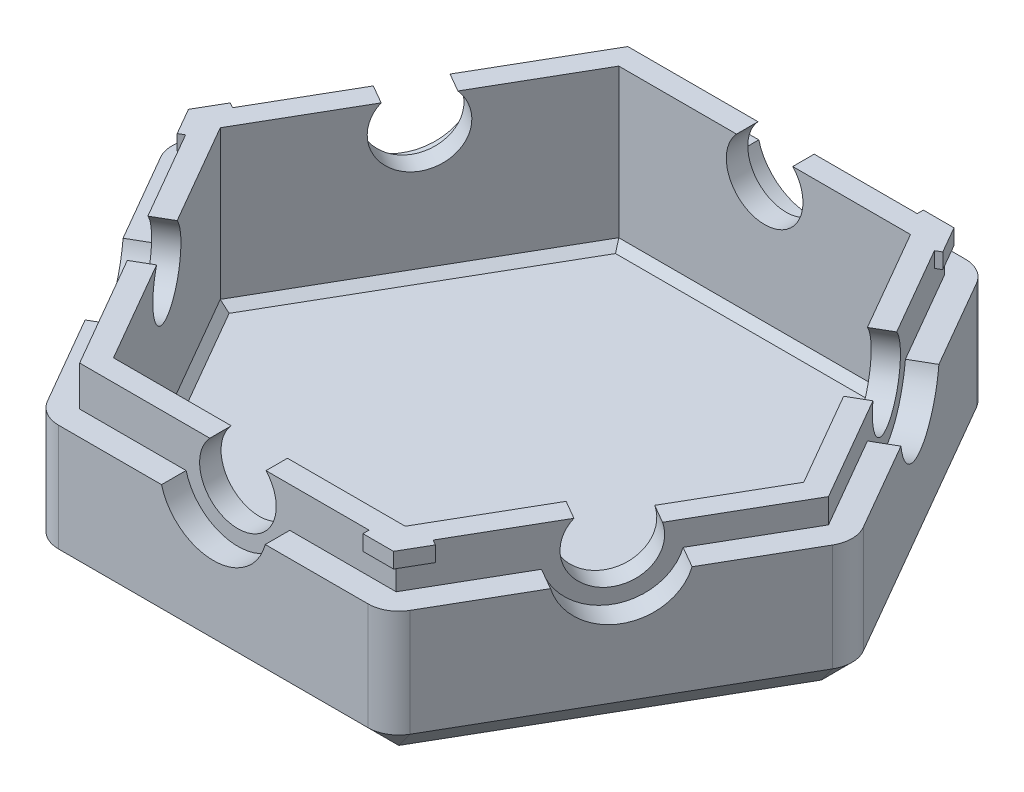
SolidWorks part; units mm, degrees
ref_plane "Front Plane" through (0, 0, 0) normal (0, 0, 1) x (1, 0, 0)
ref_plane "Top Plane" through (0, 0, 0) normal (0, 1, 0) x (1, 0, 0)
ref_plane "Right Plane" through (0, 0, 0) normal (1, 0, 0) x (0, 0, -1)
sketch "Sketch1" plane through (0, 0, 0) normal (0, 1, 0) x (1, 0, 0)
  line L0 (22.5, 0) -> (0, 0) construction
  line L1 (22.5, 0) -> (11.25, 19.4856)
  line L2 (11.25, 19.4856) -> (-11.25, 19.4856)
  line L3 (-11.25, 19.4856) -> (-22.5, 0)
  line L4 (-22.5, 0) -> (-11.25, -19.4856)
  line L5 (-11.25, -19.4856) -> (11.25, -19.4856)
  line L6 (11.25, -19.4856) -> (22.5, 0)
  circle A0 centre (0, 0) radius 19.4856 construction
  dimension "D1" = 22.5
extrude "Boss-Extrude1" add sketch "Sketch1" against normal blind 10 from offset 3.7 offset against normal yes
sketch "Sketch2" plane through (0, -3.7, 0) normal (0, 1, 0) x (1, 0, 0)
  line L0 (19.0359, 0) -> (9.5179, 16.4856)
  line L1 (9.5179, 16.4856) -> (-9.5179, 16.4856)
  line L2 (-9.5179, 16.4856) -> (-19.0359, 0)
  line L3 (-19.0359, 0) -> (-9.5179, -16.4856)
  line L4 (-9.5179, -16.4856) -> (9.5179, -16.4856)
  line L5 (9.5179, -16.4856) -> (19.0359, 0)
  line L6 (11.25, -19.4856) -> (22.5, 0)
  line L7 (22.5, 0) -> (11.25, 19.4856)
  line L8 (11.25, 19.4856) -> (-11.25, 19.4856)
  line L9 (-11.25, 19.4856) -> (-22.5, 0)
  line L10 (-22.5, 0) -> (-11.25, -19.4856)
  line L11 (-11.25, -19.4856) -> (11.25, -19.4856)
  line L12 (11.25, -19.4856) -> (22.5, 0)
  line L13 (22.5, 0) -> (11.25, 19.4856)
  line L14 (11.25, 19.4856) -> (-11.25, 19.4856)
  line L15 (-11.25, 19.4856) -> (-22.5, 0)
  line L16 (-22.5, 0) -> (-11.25, -19.4856)
  line L17 (-11.25, -19.4856) -> (11.25, -19.4856)
  dimension "D1" = 0
  dimension "D2" = 3
extrude "Cut-Extrude1" cut sketch "Sketch2" against normal blind 8.6 contours L4 L5 L0 L1 L2 L3 region at (0, -3.7, 0)
sketch "Sketch3" plane through (0, -3.7, 0) normal (0, 1, 0) x (1, 0, 0)
  line L0 (10.3262, -17.8856) -> (20.6525, 0)
  line L1 (20.6525, 0) -> (10.3262, 17.8856)
  line L2 (10.3262, 17.8856) -> (-10.3262, 17.8856)
  line L3 (-10.3262, 17.8856) -> (-20.6525, 0)
  line L4 (-20.6525, 0) -> (-10.3262, -17.8856)
  line L5 (-10.3262, -17.8856) -> (10.3262, -17.8856)
  line L6 (-9.5179, -16.4856) -> (9.5179, -16.4856)
  line L7 (-19.0359, 0) -> (-9.5179, -16.4856)
  line L8 (-9.5179, 16.4856) -> (-19.0359, 0)
  line L9 (9.5179, 16.4856) -> (-9.5179, 16.4856)
  line L10 (19.0359, 0) -> (9.5179, 16.4856)
  line L11 (9.5179, -16.4856) -> (19.0359, 0)
  line L12 (-9.5179, -16.4856) -> (9.5179, -16.4856)
  line L13 (-19.0359, 0) -> (-9.5179, -16.4856)
  line L14 (-9.5179, 16.4856) -> (-19.0359, 0)
  line L15 (9.5179, 16.4856) -> (-9.5179, 16.4856)
  line L16 (19.0359, 0) -> (9.5179, 16.4856)
  line L17 (9.5179, -16.4856) -> (19.0359, 0)
  dimension "D1" = 0
  dimension "D2" = 1.4
extrude "Boss-Extrude2" add sketch "Sketch3" along normal blind 1.6
fillet "Fillet1" radius 2 6 edges at (22.5, -8.7, 0) (11.25, -8.7, 19.4856) (-11.25, -8.7, 19.4856) (-22.5, -8.7, 0) (-11.25, -8.7, -19.4856) (11.25, -8.7, -19.4856)
sketch "Sketch6" plane through (0, -3.7, 0) normal (0, 1, 0) x (1, 0, 0)
  line L6 (10.3262, -17.8856) -> (20.6525, 0)
  line L7 (-10.3262, -17.8856) -> (10.3262, -17.8856)
  line L8 (-20.6525, 0) -> (-10.3262, -17.8856)
  line L9 (-10.3262, 17.8856) -> (-20.6525, 0)
  line L10 (10.3262, 17.8856) -> (-10.3262, 17.8856)
  line L11 (20.6525, 0) -> (10.3262, 17.8856)
  line L12 (10.3262, -17.8856) -> (20.6525, 0)
  line L13 (-10.3262, -17.8856) -> (10.3262, -17.8856)
  line L14 (-20.6525, 0) -> (-10.3262, -17.8856)
  line L15 (-10.3262, 17.8856) -> (-20.6525, 0)
  line L16 (10.3262, 17.8856) -> (-10.3262, 17.8856)
  line L17 (20.6525, 0) -> (10.3262, 17.8856)
  line L18 (11.8274, -18.4856) -> (21.9226, -1)
  line L19 (21.9226, 1) -> (11.8274, 18.4856)
  line L20 (10.0953, 19.4856) -> (-10.0953, 19.4856)
  line L21 (-11.8274, 18.4856) -> (-21.9226, 1)
  line L22 (-21.9226, -1) -> (-11.8274, -18.4856)
  line L23 (-10.0953, -19.4856) -> (10.0953, -19.4856)
  line L24 (11.8274, -18.4856) -> (21.9226, -1)
  line L25 (21.9226, 1) -> (11.8274, 18.4856)
  line L26 (10.0953, 19.4856) -> (-10.0953, 19.4856)
  line L27 (-11.8274, 18.4856) -> (-21.9226, 1)
  line L28 (-21.9226, -1) -> (-11.8274, -18.4856)
  line L29 (-10.0953, -19.4856) -> (10.0953, -19.4856)
  arc A6 (21.9226, -1) -> (21.9226, 1) centre (20.1906, 0) ccw
  arc A7 (11.8274, 18.4856) -> (10.0953, 19.4856) centre (10.0953, 17.4856) ccw
  arc A8 (-10.0953, 19.4856) -> (-11.8274, 18.4856) centre (-10.0953, 17.4856) ccw
  arc A9 (-21.9226, 1) -> (-21.9226, -1) centre (-20.1906, 0) ccw
  arc A10 (-11.8274, -18.4856) -> (-10.0953, -19.4856) centre (-10.0953, -17.4856) ccw
  arc A11 (10.0953, -19.4856) -> (11.8274, -18.4856) centre (10.0953, -17.4856) ccw
  arc A12 (21.9226, -1) -> (21.9226, 1) centre (20.1906, 0) ccw
  arc A13 (11.8274, 18.4856) -> (10.0953, 19.4856) centre (10.0953, 17.4856) ccw
  arc A14 (-10.0953, 19.4856) -> (-11.8274, 18.4856) centre (-10.0953, 17.4856) ccw
  arc A15 (-21.9226, 1) -> (-21.9226, -1) centre (-20.1906, 0) ccw
  arc A16 (-11.8274, -18.4856) -> (-10.0953, -19.4856) centre (-10.0953, -17.4856) ccw
  arc A17 (10.0953, -19.4856) -> (11.8274, -18.4856) centre (10.0953, -17.4856) ccw
  dimension "D1" = 0
  dimension "D2" = 0
extrude "Cut-Extrude4" cut sketch "Sketch6" against normal blind 1
sketch "Sketch4" plane through (0, 0, -19.4856) normal (0, 0, -1) x (-1, 0, 0)
  line L0 (0, -3.7) -> (0, -3.8) construction
  line L2 (0, -3.7) -> (0, 0) construction
  circle A0 centre (0, -3.8) radius 3.5
  dimension "D2" = 7
  dimension "D1" = 0.1
  dimension "D3" = 3.7
extrude "Cut-Extrude3" cut sketch "Sketch4" against normal up to next
ref_axis "Axis1" through (0, -14.28, 0) along (0, 1, 0)
pattern_circular "CirPattern1" count 6 over 360 about axis through (0, -14.28, 0) along (0, 1, 0) of "Cut-Extrude3"
chamfer "Chamfer1" distance 0.5 angle 45 6 edges at (-14.2769, -12.3, 8.2428) (-14.2769, -12.3, -8.2428) (0, -12.3, -16.4856) (14.2769, -12.3, -8.2428) (14.2769, -12.3, 8.2428) (0, -12.3, 16.4856)
chamfer "Chamfer2" distance 2 angle 45 12 edges at (0, -13.7, 19.4856) (11.0953, -13.7, 19.2176) (-11.0953, -13.7, 19.2176) (16.875, -13.7, 9.7428) (-16.875, -13.7, 9.7428) (22.1906, -13.7, 0) (-22.1906, -13.7, 0) (16.875, -13.7, -9.7428) (-16.875, -13.7, -9.7428) (11.0953, -13.7, -19.2176) (-11.0953, -13.7, -19.2176) (0, -13.7, -19.4856)
sketch "Sketch7" plane through (0, -2.1, 0) normal (0, 1, 0) x (1, 0, 0)
  line L124 (8.5572, 17.8856) -> (8.5572, 18.2856)
  line L125 (10.3262, 17.8856) -> (3.0594, 17.8856) construction
  line L126 (14.1446, 12.0719) -> (10.5572, 18.2856)
  line L127 (10.5572, 18.2856) -> (3.0594, 18.2856)
  line L128 (11.5572, 16.5535) -> (10.5572, 18.2856)
  line L129 (10.5572, 18.2856) -> (8.5572, 18.2856)
  line L130 (11.2108, 16.3535) -> (11.5572, 16.5535)
  line L131 (13.9597, 11.5923) -> (10.3262, 17.8856) construction
  line L132 (13.7982, 11.8719) -> (10.3262, 17.8856) construction
  line L133 (11.2108, 16.3535) -> (10.3262, 17.8856)
  line L134 (10.3262, 17.8856) -> (8.5572, 17.8856)
  line L135 (8.5572, -18.2856) -> (10.5572, -18.2856)
  line L136 (8.5572, -17.8856) -> (10.3262, -17.8856)
  line L137 (10.5572, -18.2856) -> (11.5572, -16.5535)
  line L138 (10.3262, -17.8856) -> (11.2108, -16.3535)
  line L139 (11.2108, -16.3535) -> (11.5572, -16.5535)
  line L140 (8.5572, -17.8856) -> (8.5572, -18.2856)
  line L141 (-20.1144, 1.7321) -> (-21.1144, 0)
  line L142 (-19.7679, 1.5321) -> (-20.6525, 0)
  line L143 (-21.1144, 0) -> (-20.1144, -1.7321)
  line L144 (-20.6525, 0) -> (-19.7679, -1.5321)
  line L145 (-19.7679, -1.5321) -> (-20.1144, -1.7321)
  line L146 (-19.7679, 1.5321) -> (-20.1144, 1.7321)
  point P44 (0, 0)
  dimension "D2" = 2
  dimension "D3" = 2
  dimension "D4" = 3
  dimension "D1" = 0.4
extrude "Boss-Extrude3" add sketch "Sketch7" against normal blind 1
sketch "Sketch10" plane through (0, 0, -16.4856) normal (0, 0, 1) x (1, 0, 0)
  line L0 (3.0594, -2.1) -> (1.833, -2.1)
  line L1 (-1.833, -2.1) -> (-3.0594, -2.1)
  arc A0 (-3.0594, -2.1) -> (3.0594, -2.1) centre (0, -3.8) ccw
  arc A1 (-1.833, -2.1) -> (1.833, -2.1) centre (0, -3.8) ccw
  dimension "D2" = 5
extrude "Boss-Extrude4" add sketch "Sketch10" against normal blind 1.4
pattern_circular "CirPattern5" count 6 over 360 about axis through (0, -14.28, 0) along (0, 1, 0) of "Boss-Extrude4"
sketch "Sketch9" plane through (0, -2.1, 0) normal (0, 1, 0) x (1, 0, 0)
  line L6 (16.4059, 7.3553) -> (15.1934, 6.6553)
  line L7 (15.1934, 6.6553) -> (19.0359, 0)
  line L8 (19.0359, 0) -> (15.1934, -6.6553)
  line L9 (16.4059, 7.3553) -> (15.1934, 6.6553)
  line L10 (16.4059, -7.3553) -> (20.6525, 0)
  line L11 (20.6525, 0) -> (16.4059, 7.3553)
  line L13 (15.1934, 6.6553) -> (19.0359, 0)
  line L14 (19.0359, 0) -> (15.1934, -6.6553)
  line L16 (16.4059, -7.3553) -> (20.6525, 0)
  line L17 (20.6525, 0) -> (16.4059, 7.3553)
  line L18 (15.1934, -6.6553) -> (16.4059, -7.3553)
  line L19 (15.1934, -6.6553) -> (16.4059, -7.3553)
  dimension "D1" = 0
extrude "Cut-Extrude5" cut sketch "Sketch9" against normal blind 1
